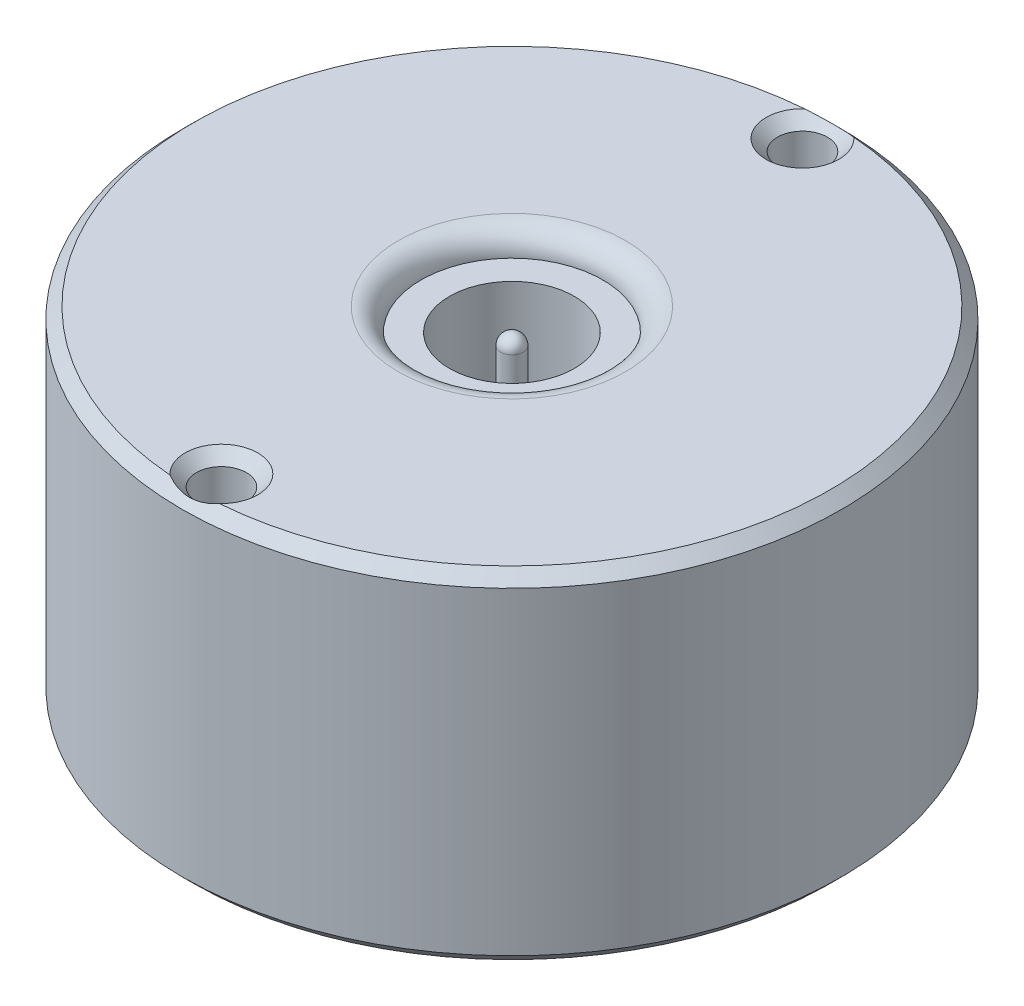
SolidWorks part; units mm, degrees
ref_plane "Front Plane" through (0, 0, 0) normal (0, 0, 1) x (1, 0, 0)
ref_plane "Top Plane" through (0, 0, 0) normal (0, 1, 0) x (1, 0, 0)
ref_plane "Right Plane" through (0, 0, 0) normal (1, 0, 0) x (0, 0, -1)
sketch "Sketch1" plane through (0, 0, 0) normal (0, 1, 0) x (1, 0, 0)
  circle A0 centre (0, 0) radius 14.5
  dimension "D1" = 29
extrude "Boss-Extrude1" add sketch "Sketch1" along normal blind 15
sketch "Sketch2" plane through (0, 15, 0) normal (0, 1, 0) x (1, 0, 0)
  line L1 (-12.75, -0.9) -> (12.75, -0.9)
  line L2 (-12.75, -0.9) -> (-12.75, 0.9)
  line L3 (-12.75, 0.9) -> (12.75, 0.9)
  line L4 (12.75, -0.9) -> (12.75, 0.9)
  line L5 (-12.75, -0.9) -> (12.75, 0.9) construction
  line L6 (-12.75, 0.9) -> (12.75, -0.9) construction
  circle A0 centre (0, 0) radius 12.7817
  circle A1 centre (0, 12.7817) radius 1.1
  circle A2 centre (0, -12.7817) radius 1.1
  point P0 (0, 0)
  dimension "D3" = 2.2
  dimension "D4" = 2.2
  dimension "D1" = 1.8
  dimension "D2" = 25.5
extrude "Cut-Extrude1" cut sketch "Sketch2" against normal blind 15 contours A0 A2 | A0 A2 | A0 A1 | A0 A1 region at (0, 15, 12.3064) region at (0, 15, 13.24) region at (0, 15, -13.24) region at (0, 15, -12.3064)
chamfer "Chamfer1" distance 0.5 angle 45 2 edges at (0, 15, 13.8817) (0, 15, -11.6817)
chamfer "Chamfer2" distance 0.5 angle 45 2 edges at (0, 0, 14.5) (0, 15, 14.5)
sketch "Sketch3" plane through (0, 15, 0) normal (0, 1, 0) x (1, 0, 0)
  circle A0 centre (0, 0) radius 2.75
  circle A1 centre (0, 0) radius 0.5
  dimension "D1" = 5.5
  dimension "D2" = 1
extrude "Cut-Extrude2" cut sketch "Sketch3" against normal blind 5
sketch "Sketch4" plane through (0, 15, 0) normal (0, 1, 0) x (1, 0, 0)
  circle A0 centre (0, 0) radius 4
  dimension "D1" = 8
extrude "Cut-Extrude3" cut sketch "Sketch4" against normal blind 1
fillet "Fillet1" radius 1 1 edges at (0, 15, 4)
fillet "Fillet2" radius 0.5 1 edges at (0, 14, 0.5)
